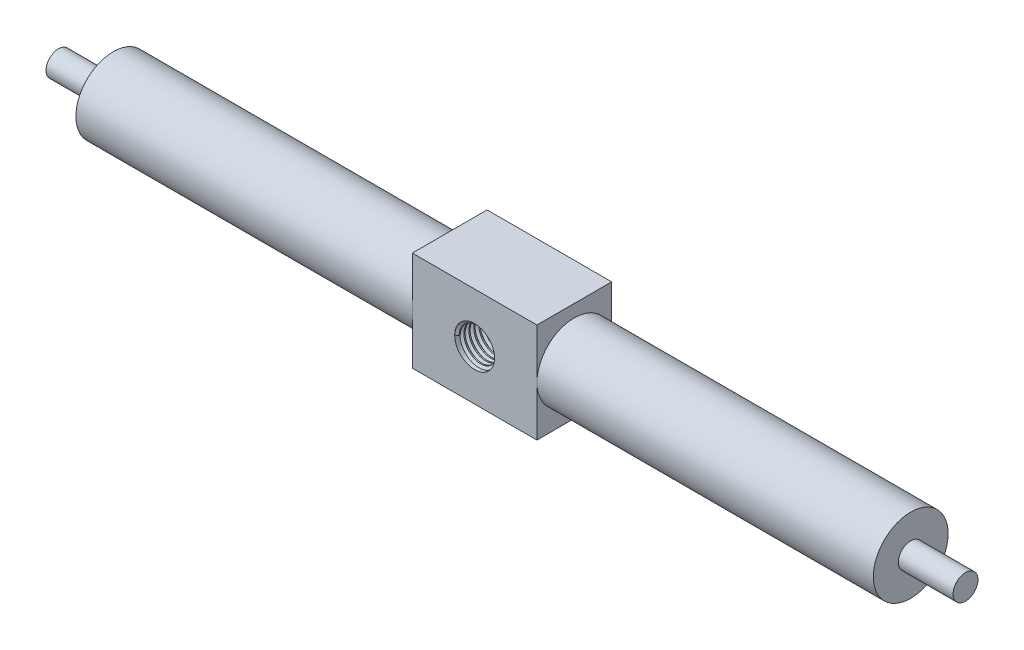
SolidWorks part; units mm, degrees
ref_plane "Front Plane" through (0, 0, 0) normal (0, 0, 1) x (1, 0, 0)
ref_plane "Top Plane" through (0, 0, 0) normal (0, 1, 0) x (1, 0, 0)
ref_plane "Right Plane" through (0, 0, 0) normal (1, 0, 0) x (0, 0, -1)
sketch "Sketch1" plane through (0, 0, 0) normal (0, 0, 1) x (1, 0, 0)
  line L0 (203.6676, 133.4309) -> (-160.3324, 133.4309)
  line L10 (203.6676, 133.4309) -> (203.6676, 138.4309)
  line L13 (-160.3324, 133.4309) -> (163.6676, 133.4309) construction
  line L14 (203.6676, 138.4309) -> (181.6676, 138.4309)
  line L15 (181.6676, 138.4309) -> (181.6676, 148.4309)
  line L21 (-160.3324, 133.4309) -> (-160.3324, 138.4309)
  line L22 (-160.3324, 138.4309) -> (-138.3324, 138.4309)
  line L23 (-138.3324, 138.4309) -> (-138.3324, 148.4309)
  line L24 (181.6676, 148.4309) -> (-138.3324, 148.4309)
  point P17 (21.6676, 133.4309)
  point P20 (-34.5089, 153.4309)
  dimension "D1" = 10
  dimension "D3" = 22
  dimension "D4" = 364
  dimension "D5" = 320
revolve "Revolve2" add sketch "Sketch1" angle 360 about L0
sketch "Sketch4" plane through (0, 0, 0) normal (0, 0, 1) x (1, 0, 0)
  line L1 (-3.3324, 153.4309) -> (46.6676, 153.4309)
  line L2 (-3.3324, 153.4309) -> (-3.3324, 113.4309)
  line L3 (-3.3324, 113.4309) -> (46.6676, 113.4309)
  line L4 (46.6676, 153.4309) -> (46.6676, 113.4309)
  line L5 (-3.3324, 153.4309) -> (46.6676, 113.4309) construction
  line L6 (-3.3324, 113.4309) -> (46.6676, 153.4309) construction
  point P0 (21.6676, 133.4309)
  dimension "D2" = 50
extrude "Boss-Extrude2" add sketch "Sketch4" along normal mid plane 30
sketch "Sketch5" plane through (0, 0, 15) normal (0, 0, 1) x (1, 0, 0)
  circle A0 centre (21.6676, 133.4309) radius 8
  dimension "D1" = 16
extrude "Cut-Extrude2" cut sketch "Sketch5" against normal blind 58
thread "Thread2" pitch 2 method extrude profile "Thread Profile2" start angle 0, offset 0, length 30, pitch 2, diameter 16
ref_plane "Plane2" through (13.6676, 133.4309, 15) normal (0, -1, 0) x (-1, 0, 0)
sketch "Thread Profile2" plane through (13.6676, 133.4309, 15) normal (0, -1, 0) x (-1, 0, 0)
  line L0 (0, 0) -> (0, 2) construction
  line L11 (0, 0) -> (0, 1.75)
  line L12 (0, 1.75) -> (-1.0825, 1.125)
  line L13 (-1.0825, 1.125) -> (-1.0825, 0.625)
  line L15 (-1.0825, 0.625) -> (0, 0)
  line L17 (-1.0825, 0.875) -> (0, 0.875) construction
  point P2 (0, 0)
  dimension "Pitch" = 2
  dimension "Profile_Angle" = 60
  dimension "Profile_Land" = 0.5
  dimension "Profile_Height" = 1.0825
